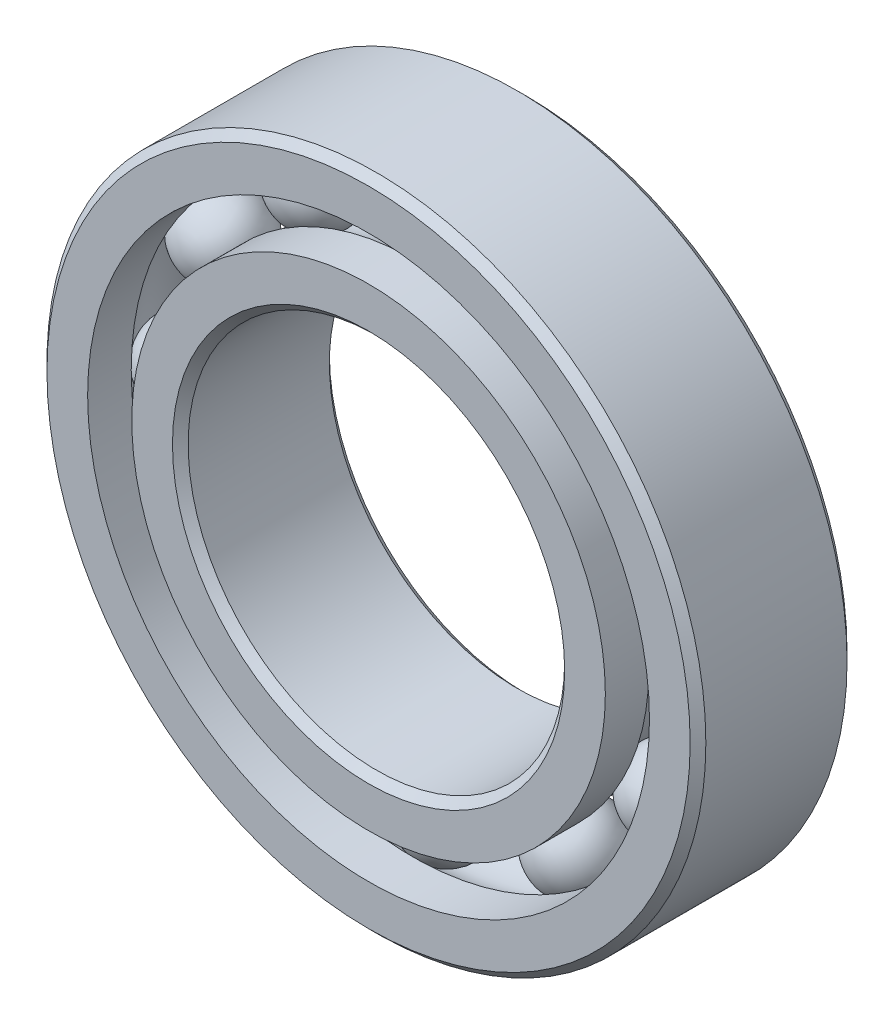
SolidWorks part; units mm, degrees
ref_plane "Front Plane" through (0, 0, 0) normal (0, 0, 1) x (1, 0, 0)
ref_plane "Top Plane" through (0, 0, 0) normal (0, 1, 0) x (1, 0, 0)
ref_plane "Right Plane" through (0, 0, 0) normal (1, 0, 0) x (0, 0, -1)
sketch "Sketch1" plane through (0, 0, 0) normal (1, 0, 0) x (0, 0, -1)
  line L0 (-2.5, 0) -> (2.5, 0) construction
  line L1 (0, 10.5) -> (0, -10.5) construction
  line L2 (2.25, 10.5) -> (-2.25, 10.5)
  line L3 (-2.25, 10.5) -> (-2.5, 10.25)
  line L4 (-2.5, 10.25) -> (-2.5, 8.9533)
  line L5 (-2.5, 8.9533) -> (-1.1111, 8.9533)
  line L6 (2.5, 8.9533) -> (1.1111, 8.9533)
  line L7 (2.5, 10.25) -> (2.5, 8.9533)
  line L8 (2.25, 10.5) -> (2.5, 10.25)
  line L9 (0, 10.5) -> (0, 8.25) construction
  line L10 (0, 8.25) -> (0, 6) construction
  arc A0 (-1.1111, 8.9533) -> (1.1111, 8.9533) centre (0, 8.25) cw
  point P14 (0, 6)
  dimension "D3" = 2.2222
  dimension "D1" = 45
  dimension "Width" = 5
  dimension "OD" = 21
  dimension "D2" = 0.25
  dimension "Shaft Dia" = 12
  dimension "D4" = 0.7033
revolve "Revolve1" add sketch "Sketch1" angle 360 about L0
sketch "Sketch3" plane through (0, 0, 0) normal (1, 0, 0) x (0, 0, -1)
  line L0 (-2.5, 7.5467) -> (-1.1111, 7.5467)
  line L1 (0, 10.5) -> (0, -10.5) construction
  line L2 (-2.5, 10.25) -> (-2.5, 8.9533) construction
  line L3 (-2.5, 7.5467) -> (-2.5, 6.25)
  line L4 (-2.25, 10.5) -> (-2.5, 10.25) construction
  line L5 (-2.5, 6.25) -> (-2.25, 6)
  line L6 (-2.25, 6) -> (2.25, 6)
  line L7 (2.25, 10.5) -> (2.25, -10.5) construction
  line L8 (2.25, 6) -> (2.5, 6.25)
  line L9 (2.5, -10.25) -> (2.5, 10.25) construction
  line L10 (2.5, 6.25) -> (2.5, 7.5467)
  line L11 (2.5, 7.5467) -> (1.1111, 7.5467)
  line L13 (2.25, 10.5) -> (2.5, 10.25) construction
  arc A0 (1.1111, 8.9533) -> (-1.1111, 8.9533) centre (0, 8.25) ccw construction
  arc A1 (1.1111, 7.5467) -> (-1.1111, 7.5467) centre (0, 8.25) cw
revolve "Revolve3" add sketch "Sketch3" angle 360 about L0
sketch "Sketch4" plane through (0, 0, 0) normal (1, 0, 0) x (0, 0, -1)
  line L0 (-1.315, 8.25) -> (1.315, 8.25)
  arc A2 (-1.315, 8.25) -> (1.315, 8.25) centre (0, 8.25) cw
  arc A3 (1.1111, 8.9533) -> (-1.1111, 8.9533) centre (0, 8.25) ccw construction
revolve "Revolve4" add sketch "Sketch4" angle 360 about L0
ref_axis "Axis1" through (0, 0, -2.5) along (0, 0, 1)
pattern_circular "CirPattern1" count 12 every 30 about axis through (0, 0, -2.5) along (0, 0, 1) of bodies 104
sketch "Sketch5" plane through (0, 0, 0) normal (1, 0, 0) x (0, 0, -1)
  line L0 (-2.5, 8.9533) -> (-1.1111, 8.9533) construction
  line L1 (-2.375, 8.9533) -> (-1.315, 8.9533)
  line L2 (-2.375, 8.9533) -> (-2.375, 7.5467)
  line L3 (-2.375, 7.5467) -> (-1.315, 7.5467)
  line L4 (-1.315, 8.9533) -> (-1.315, 7.5467)
  line L5 (-2.5, 7.5467) -> (-1.1111, 7.5467) construction
  line L6 (2.5, 8.9533) -> (1.1111, 8.9533) construction
  line L7 (2.375, 8.9533) -> (1.315, 8.9533)
  line L8 (2.375, 8.9533) -> (2.375, 7.5467)
  line L9 (2.375, 7.5467) -> (1.315, 7.5467)
  line L10 (1.315, 8.9533) -> (1.315, 7.5467)
  line L11 (2.5, 7.5467) -> (1.1111, 7.5467) construction
  line L12 (-2.25, 10.5) -> (-2.5, 10.25) construction
  point P18 (-2.375, 10.375)
equation "\"D2@Sketch1\" = \"Width@Sketch1\"*.05"
equation "\"D3@Sketch1\" = \"Width@Sketch1\"/2.25"
equation "\"D4@Sketch1\" = (((\"OD@Sketch1\"-\"Width@Sketch1\")/2)/3.25)/3.5"
equation "\"D2@CirPattern1\" = 360/\"Balls@CirPattern1\""
